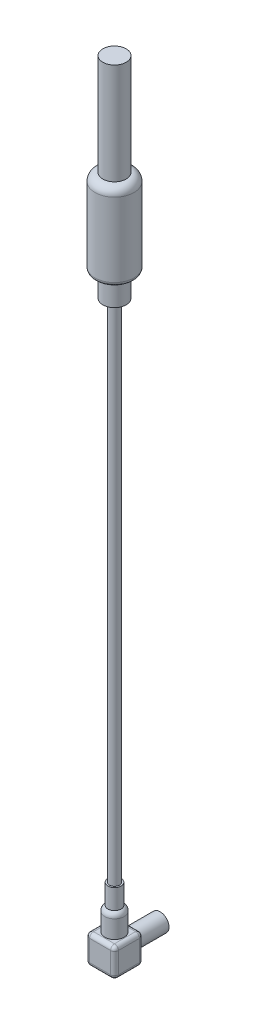
SolidWorks part; units mm, degrees
ref_plane "Front Plane" through (0, 0, 0) normal (0, 0, 1) x (1, 0, 0)
ref_plane "Top Plane" through (0, 0, 0) normal (0, 1, 0) x (1, 0, 0)
ref_plane "Right Plane" through (0, 0, 0) normal (1, 0, 0) x (0, 0, -1)
sketch "Sketch1" plane through (0, 0, 0) normal (0, 0, 1) x (1, 0, 0)
  circle A0 centre (0, 0) radius 1.15
  dimension "D1" = 2.3
extrude "Boss-Extrude1" add sketch "Sketch1" along normal blind 4
sketch "Sketch2" plane through (0, 0, 4) normal (0, 0, 1) x (1, 0, 0)
  line L1 (1.85, -1.85) -> (-1.85, -1.85)
  line L2 (1.85, -1.85) -> (1.85, 1.85)
  line L3 (1.85, 1.85) -> (-1.85, 1.85)
  line L4 (-1.85, -1.85) -> (-1.85, 1.85)
  line L5 (1.85, -1.85) -> (-1.85, 1.85) construction
  line L6 (1.85, 1.85) -> (-1.85, -1.85) construction
  point P0 (0, 0)
  dimension "D1" = 3.7
  dimension "D2" = 3.7
extrude "Boss-Extrude2" add sketch "Sketch2" along normal blind 3.7
fillet "Fillet1" radius 0.5 12 edges at (-1.85, 0, 4) (0, 1.85, 4) (1.85, 0, 4) (0, -1.85, 4) (-1.85, -1.85, 5.85) (1.85, -1.85, 5.85) (1.85, 0, 7.7) (-1.85, 0, 7.7) (0, -1.85, 7.7) (0, 1.85, 7.7) (-1.85, 1.85, 5.85) (1.85, 1.85, 5.85)
sketch "Sketch3" plane through (0, 1.85, 0) normal (0, 1, 0) x (1, 0, 0)
  line L0 (0, -4.5) -> (0, -7.2) construction
  line L1 (1.35, -4.5) -> (-1.35, -4.5) construction
  line L2 (-1.35, -7.2) -> (1.35, -7.2) construction
  circle A0 centre (0, -5.85) radius 1.25
  dimension "D1" = 2.5
extrude "Boss-Extrude3" add sketch "Sketch3" along normal blind 3
fillet "Fillet2" radius 0.7 1 edges at (-1.25, 4.85, 5.85)
sketch "Sketch4" plane through (0, 4.85, 0) normal (0, 1, 0) x (1, 0, 0)
  line L0 (0, -5.3) -> (0, -6.4) construction
  circle A0 centre (0, -5.85) radius 0.55 construction
  circle A1 centre (0, -5.85) radius 0.85
  dimension "D1" = 1.7
extrude "Boss-Extrude4" add sketch "Sketch4" along normal blind 2.5 and the other way up to surface other way up to face at (-1.25, 4.15, 5.85)
sketch "Sketch5" plane through (0, 7.35, 0) normal (0, 1, 0) x (1, 0, 0)
  circle A0 centre (0, -5.85) radius 0.65
  dimension "D1" = 1.3
extrude "Boss-Extrude5" add sketch "Sketch5" along normal blind 65
sketch "Sketch6" plane through (0, 72.35, 0) normal (0, 1, 0) x (1, 0, 0)
  circle A0 centre (0, -5.85) radius 1.5
  dimension "D1" = 3
extrude "Boss-Extrude6" add sketch "Sketch6" along normal blind 3
sketch "Sketch7" plane through (0, 75.35, 0) normal (0, 1, 0) x (1, 0, 0)
  line L0 (0, -4.35) -> (0, -7.35) construction
  circle A0 centre (0, -5.85) radius 1.5 construction
  circle A1 centre (0, -5.85) radius 2.5
  dimension "D1" = 5
extrude "Boss-Extrude7" add sketch "Sketch7" along normal blind 11
sketch "Sketch8" plane through (0, 86.35, 0) normal (0, 1, 0) x (1, 0, 0)
  circle A0 centre (0, -5.85) radius 1.5
  dimension "D1" = 3
extrude "Boss-Extrude8" add sketch "Sketch8" along normal blind 13
fillet "Fillet3" radius 1 1 edges at (-2.5, 86.35, 5.85)
fillet "Fillet4" radius 0.5 1 edges at (-2.5, 75.35, 5.85)
fillet "Fillet5" radius 0.5 1 edges at (-1.5, 75.35, 5.85)
